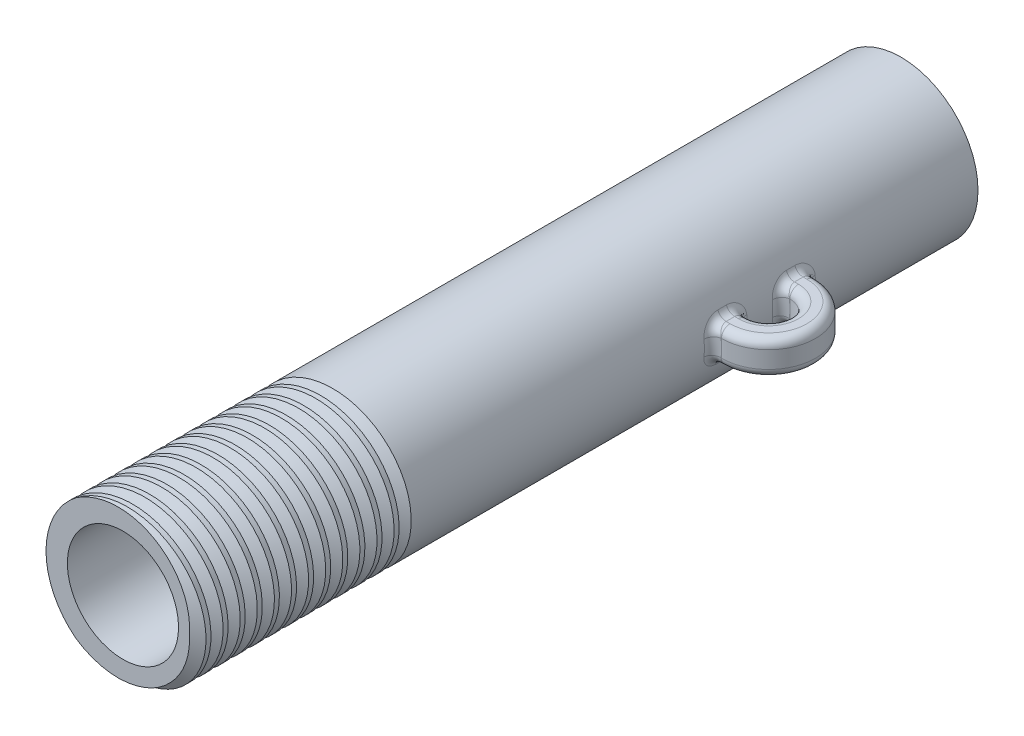
SolidWorks part; units mm, degrees
ref_plane "Front Plane" through (0, 0, 0) normal (0, 0, 1) x (1, 0, 0)
ref_plane "Top Plane" through (0, 0, 0) normal (0, 1, 0) x (1, 0, 0)
ref_plane "Right Plane" through (0, 0, 0) normal (1, 0, 0) x (0, 0, -1)
sketch "Sketch1" plane through (0, 0, 0) normal (0, 0, 1) x (1, 0, 0)
  circle A0 centre (0, 0) radius 6.5
  circle A1 centre (0, 0) radius 9
  dimension "D1" = 18
  dimension "D2" = 13
extrude "Boss-Extrude1" add sketch "Sketch1" along normal blind 91
sketch "Sketch2" plane through (0, 0, 91) normal (0, 0, 1) x (1, 0, 0)
  circle A0 centre (0, 0) radius 9
  circle A2 centre (0, 0) radius 9 construction
curve "Helix/Spiral1" pitch 2 height 25 radius 9 centre (0, 0, 91) axis (0, 0, -1) start towards (1, 0, 0)
sketch "Sketch5" plane through (0, 0, 0) normal (0, 1, 0) x (1, 0, 0)
  line L0 (-9, -72.0961) -> (9, -72.0961) construction
  line L2 (-9, 0) -> (-9, -91) construction
  line L9 (9, -91) -> (9, 0) construction
  line L10 (0, -72.0961) -> (0, -75.3544) construction
  line L12 (7.773, -91) -> (9.1892, -90.1824)
  line L13 (9.1892, -90.1824) -> (9.1892, -91.8176)
  line L14 (9.1892, -91.8176) -> (7.773, -91)
  line L15 (-9, -91) -> (9, -91) construction
  dimension "D1" = 60
  dimension "D2" = 7.773
sweep "Cut-Sweep4" cut profiles "Sketch5" path "Helix/Spiral1" align with end faces yes
sketch "Sketch6" plane through (0, 0, 0) normal (0, 1, 0) x (1, 0, 0)
  line L0 (10, -20) -> (7, -20)
  line L1 (7, -20) -> (7, -23)
  line L2 (7, -23) -> (10, -23)
  line L3 (10, -28) -> (7, -28)
  line L4 (7, -28) -> (7, -31)
  line L5 (7, -31) -> (10, -31)
  line L6 (9, -66.2916) -> (9, 0) construction
  line L7 (9, 0) -> (-9, 0) construction
  arc A0 (10, -23) -> (10, -28) centre (10, -25.5) cw
  arc A1 (10, -20) -> (10, -31) centre (10, -25.5) cw
  dimension "D1" = 3
  dimension "D2" = 5
  dimension "D3" = 2
  dimension "D4" = 3
  dimension "D5" = 20
extrude "Boss-Extrude2" add sketch "Sketch6" along normal blind 2 and the other way blind 2
fillet "Fillet1" radius 1 20 edges at (8.775, 2, 29.5) (8.775, 2, 21.5) (9, 0, 23) (9, 0, 28) (9, 0, 31) (9, 0, 20) (9.3875, -2, 23) (9.3875, -2, 28) (9.3875, -2, 31) (9.3875, -2, 20) (9.3875, 2, 31) (9.3875, 2, 20) (9.3875, 2, 23) (9.3875, 2, 28) (8.775, -2, 29.5) (8.775, -2, 21.5) (12.5, -2, 25.5) (15.5, -2, 25.5) (15.5, 2, 25.5) (12.5, 2, 25.5)
